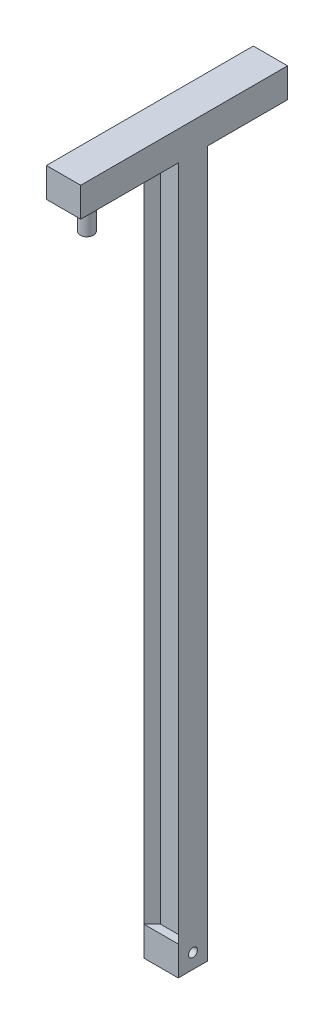
SolidWorks part; units mm, degrees
ref_plane "Front Plane" through (0, 0, 0) normal (0, 0, 1) x (1, 0, 0)
ref_plane "Top Plane" through (0, 0, 0) normal (0, 1, 0) x (1, 0, 0)
ref_plane "Right Plane" through (0, 0, 0) normal (1, 0, 0) x (0, 0, -1)
sketch "Sketch1" plane through (0, 0, 0) normal (0, 1, 0) x (1, 0, 0)
  line L0 (0, 0) -> (-2.8284, -2.8284)
  line L1 (-2.8284, -2.8284) -> (-8.8284, -2.8284)
  line L2 (-8.8284, -2.8284) -> (-11.6569, 0)
  line L3 (-11.6569, 0) -> (-11.6569, -10)
  line L4 (-11.6569, -10) -> (-8.8284, -7.1716)
  line L5 (-8.8284, -7.1716) -> (-2.8284, -7.1716)
  line L6 (-2.8284, -7.1716) -> (0, -10)
  line L7 (0, -10) -> (0, 0)
  dimension "D1" = 6
  dimension "D2" = 6
  dimension "D3" = 135
  dimension "D4" = 135
  dimension "D5" = 10
  dimension "D6" = 10
  dimension "D7" = 4
  dimension "D8" = 4
extrude "Boss-Extrude1" add sketch "Sketch1" along normal blind 240
sketch "Sketch2" plane through (0, 0, 0) normal (0, -1, 0) x (1, 0, 0)
  line L1 (0, 0) -> (-11.6569, 0)
  line L2 (0, 0) -> (0, 10)
  line L3 (0, 10) -> (-11.6569, 10)
  line L4 (-11.6569, 0) -> (-11.6569, 10)
extrude "Boss-Extrude2" add sketch "Sketch2" along normal blind 10
sketch "Sketch3" plane through (-11.6569, 0, 0) normal (-1, 0, 0) x (0, 0, 1)
  line L0 (10, -10) -> (0, -10) construction
  line L2 (0, -10) -> (0, 0) construction
  circle A0 centre (5, -5) radius 1.5
  point P4 (5, -10)
  point P7 (0, -5)
  dimension "D1" = 0
  dimension "D2" = 0
  dimension "D3" = 3
extrude "Cut-Extrude1" cut sketch "Sketch3" against normal blind 30
sketch "Sketch4" plane through (0, 0, 2.8284) normal (0, 0, -1) x (-1, 0, 0)
  line L0 (0, 240) -> (0, 0) construction
  line L1 (0, 240) -> (11.6569, 240)
  line L2 (0, 240) -> (0, 230)
  line L3 (0, 230) -> (11.6569, 230)
  line L4 (11.6569, 240) -> (11.6569, 230)
  line L5 (11.6569, 240) -> (11.6569, 0) construction
  line L6 (2.8284, 240) -> (8.8284, 240) construction
  dimension "D1" = 0
  dimension "D2" = 0
  dimension "D3" = 0
  dimension "D4" = 10
extrude "Boss-Extrude3" add sketch "Sketch4" along normal blind 30
sketch "Sketch5" plane through (0, 0, 7.1716) normal (0, 0, 1) x (1, 0, 0)
  line L0 (0, 240) -> (0, 0) construction
  line L1 (0, 240) -> (-11.6569, 240)
  line L2 (0, 240) -> (0, 230)
  line L3 (0, 230) -> (-11.6569, 230)
  line L4 (-11.6569, 240) -> (-11.6569, 230)
  line L5 (-8.8284, 240) -> (-2.8284, 240) construction
  dimension "D1" = 0
  dimension "D2" = 0
  dimension "D3" = 0
  dimension "D4" = 10
extrude "Boss-Extrude4" add sketch "Sketch5" along normal blind 36
sketch "Sketch7" plane through (0, 230, 0) normal (0, -1, 0) x (1, 0, 0)
  line L0 (-11.6569, 43.1716) -> (0, 43.1716) construction
  circle A0 centre (-8.335, 32.7116) radius 2.25
  dimension "D1" = 10.46
  dimension "D2" = 4.5
extrude "Boss-Extrude6" add sketch "Sketch7" along normal blind 13
sketch "Sketch8" plane through (0, 0, -27.1716) normal (0, 0, -1) x (-1, 0, 0)
  line L0 (0, 230) -> (11.6569, 230) construction
  line L1 (11.6569, 230) -> (11.6569, 240) construction
  circle A0 centre (5.8284, 235) radius 2.75
  point P4 (5.8284, 230)
  point P7 (11.6569, 235)
  dimension "D1" = 0
  dimension "D2" = 0
  dimension "D3" = 5.5
extrude "Cut-Extrude2" cut sketch "Sketch8" against normal blind 10
sketch "Sketch9" plane through (0, 230, 0) normal (0, -1, 0) x (-1, 0, 0)
  circle A0 centre (8.335, -32.7116) radius 3.5
  dimension "D1" = 7
extrude "Boss-Extrude7" add sketch "Sketch9" along normal blind 3
thread "Thread1" pitch 2.1167 method cut profile "Thread Profile1" start angle 0, offset 0, length 8, pitch 2.1167, diameter 5.5
ref_plane "Plane1" through (-3.0784, 235, -27.1716) normal (0, -1, 0) x (1, 0, 0)
sketch "Thread Profile1" plane through (-3.0784, 235, -27.1716) normal (0, -1, 0) x (1, 0, 0)
  line L0 (0, 0) -> (0, 2.1167) construction
  line L1 (0, 0) -> (1.1457, 0.6615)
  line L2 (1.1457, 0.6615) -> (1.1457, 0.926)
  line L3 (1.1457, 0.926) -> (0, 1.5875)
  line L4 (1.1457, 0.7937) -> (0, 0.7937) construction
  line L11 (0, 0) -> (0, 1.5875)
  point P2 (0, 0)
  dimension "Pitch" = 2.1167
  dimension "Profile_Angle" = 60
  dimension "Profile_Land" = 0.2646
  dimension "Profile_Height" = 1.1457
sketch "Sketch12" plane through (0, 0, -27.1716) normal (0, 0, -1) x (-1, 0, 0)
  circle A0 centre (5.8284, 235) radius 3.75
  dimension "D1" = 7.5
extrude "Cut-Extrude3" cut sketch "Sketch12" against normal blind 2
